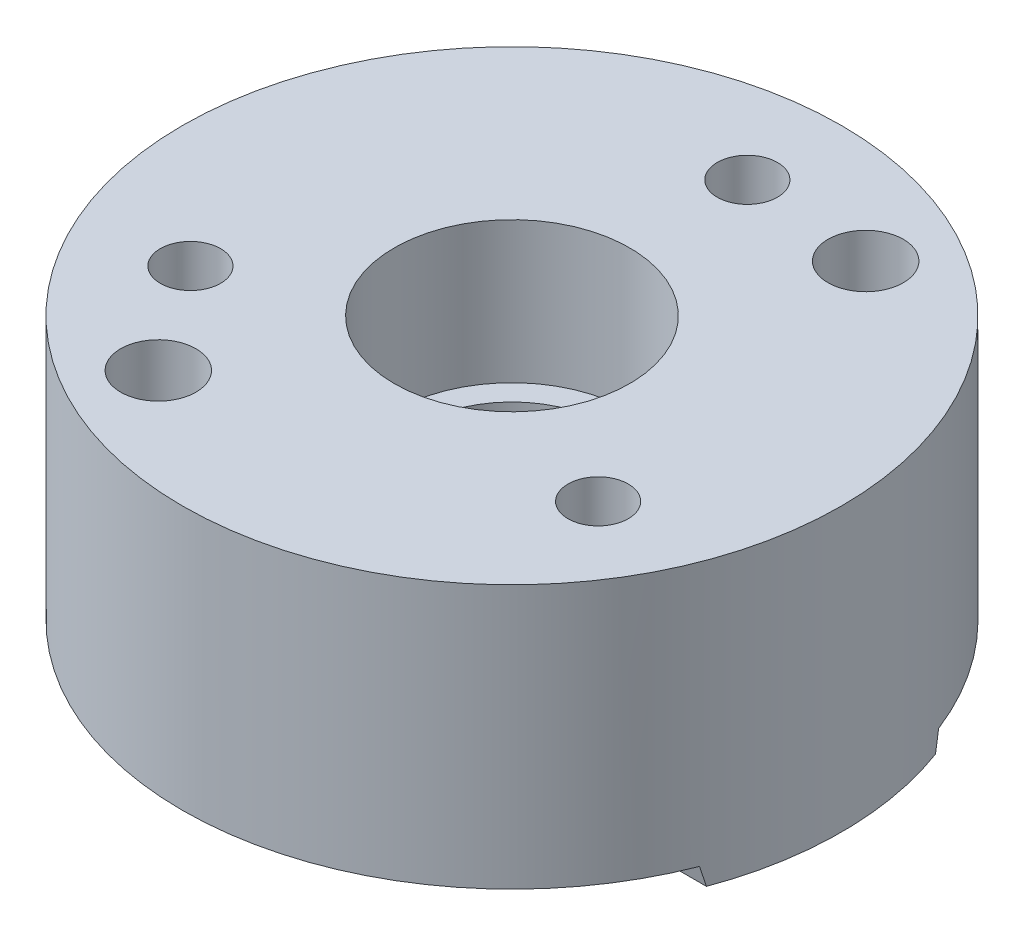
SolidWorks part; units mm, degrees
material "K110"
ref_plane "Front Plane" through (0, 0, 0) normal (0, 0, 1) x (1, 0, 0)
ref_plane "Top Plane" through (0, 0, 0) normal (0, 1, 0) x (1, 0, 0)
ref_plane "Right Plane" through (0, 0, 0) normal (1, 0, 0) x (0, 0, -1)
sketch "Sketch1" plane through (0, 0, 0) normal (0, 1, 0) x (1, 0, 0)
  circle A0 centre (0, 0) radius 35
  circle A1 centre (0, 0) radius 10
  dimension "D1" = 20
  dimension "D2" = 70
extrude "Boss-Extrude1" add sketch "Sketch1" against normal blind 30
sketch "Sketch4" plane through (0, 0, 0) normal (0, 1, 0) x (1, 0, 0)
  circle A0 centre (0, 0) radius 12.5
  dimension "D1" = 25
extrude "Cut-Extrude2" cut sketch "Sketch4" against normal blind 15
hole_wizard "CBORE for M6 Hex Socket Head Cap Screw1" positions "Sketch15" profile "Sketch8" counterbore size "M6" standard "ISO" end condition through all
sketch "Sketch15" plane through (0, -30, 0) normal (0, -1, 0) x (-1, 0, 0)
  line L0 (0, 25) -> (0, 0) construction
  line L1 (0, 0) -> (-21.6506, -12.5) construction
  line L3 (0, 0) -> (21.6506, -12.5) construction
  circle A0 centre (0, 0) radius 25 construction
  point P0 (0, 25)
  point P2 (21.6506, -12.5)
  point P4 (-21.6506, -12.5)
  dimension "D1" = 50
  dimension "D2" = 120
  dimension "D3" = 120
sketch "Sketch8" plane through (0, -30, -25) normal (1, 0, 0) x (0, 0, -1)
  line L0 (0, 0) -> (0, 30)
  line L1 (0, 30) -> (3.2, 30)
  line L3 (3.2, 30) -> (3.2, 8.4)
  line L4 (3.2, 8.4) -> (5.5, 8.4)
  line L5 (5.5, 8.4) -> (5.5, 0)
  line L7 (5.5, 0) -> (0, 0)
  line L11 (0, -6.35) -> (0, 107.95) construction
  dimension "Thru Hole Dia." = 6.4
  dimension "Thru Hole Depth" = 30
  dimension "C'Bore Dia." = 11
  dimension "C'Bore Depth" = 8.4
hole_wizard "Ø8.0mm Dowel Hole1" positions "Sketch17" profile "Sketch12" hole size "Ø8.0" standard "ISO" end condition through all
sketch "Sketch17" plane through (0, -30, 0) normal (0, -1, 0) x (-1, 0, 0)
  line L0 (-13.75, 23.8157) -> (13.75, -23.8157) construction
  line L1 (0, 35) -> (0, -35) construction
  circle A0 centre (0, 0) radius 27.5 construction
  circle A1 centre (0, 0) radius 35 construction
  point P0 (13.75, -23.8157)
  point P2 (-13.75, 23.8157)
  point P26 (0, 0)
  dimension "D1" = 55
  dimension "D2" = 30
sketch "Sketch12" plane through (-13.75, -30, 23.8157) normal (1, 0, 0) x (0, 0, -1)
  line L0 (0, 0) -> (0, 30)
  line L1 (0, 30) -> (4, 30)
  line L2 (4, 30) -> (4, 0)
  line L5 (4, 0) -> (0, 0)
  line L11 (0, -6.35) -> (0, 107.95) construction
  dimension "Thru Hole Dia." = 8
  dimension "Thru Hole Depth" = 30
sketch "Sketch14" plane through (0, -30, 0) normal (0, -1, 0) x (1, 0, 0)
  line L0 (-58.6405, -12.7) -> (-12.0399, -12.7) construction
  line L1 (-35, 12.7) -> (35, 12.7)
  line L2 (-35, 12.7) -> (-35, -12.7)
  line L3 (-35, -12.7) -> (35, -12.7)
  line L4 (35, 12.7) -> (35, -12.7)
  line L5 (-35, 12.7) -> (35, -12.7) construction
  line L6 (-35, -12.7) -> (35, 12.7) construction
  circle A0 centre (0, 0) radius 35 construction
  point P0 (0, 0)
extrude "Cut-Extrude3" cut sketch "Sketch14" against normal blind 2 flip side to cut
sketch "Sketch16" plane through (0, -30, 0) normal (0, -1, 0) x (1, 0, 0)
  circle A0 centre (22.5, 0) radius 4.25
  dimension "D1" = 8.5
sketch "Sketch18" plane through (0, -30, 0) normal (0, -1, 0) x (1, 0, 0)
  circle A1 centre (-25.9, 0) radius 4.25
  dimension "D1" = 8.5
extrude "Cut-Extrude5" cut sketch "Sketch18" against normal blind 6
sketch "Sketch19" plane through (0, 0, 0) normal (1, 0, 0) x (0, 0, -1)
  line L2 (-12.7, -28) -> (-12.1641, -30)
  line L3 (-12.7, -30) -> (12.7, -30) construction
  line L4 (-12.1641, -30) -> (-12.7, -30)
  line L5 (-12.7, -30) -> (-12.7, -28)
  line L6 (12.7, -28) -> (12.1641, -30)
  line L7 (12.1641, -30) -> (12.7, -30)
  line L8 (12.7, -30) -> (12.7, -28)
  dimension "D1" = 15
  dimension "D2" = 15
extrude "Cut-Extrude6" cut sketch "Sketch19" against normal through all both and the other way through all
sketch "Sketch20" plane through (0, -30, 0) normal (0, -1, 0) x (1, 0, 0)
  line L0 (-16.1609, 12.1641) -> (16.1609, 12.1641) construction
  line L1 (-12.5811, 12.1641) -> (12.5811, 12.1641)
  line L2 (-32.8182, -12.1641) -> (32.8182, -12.1641) construction
  line L3 (-12.5811, -12.1641) -> (12.5811, -12.1641)
  arc A0 (12.5811, 12.1641) -> (-12.5811, 12.1641) centre (0, 0) ccw
  arc A1 (-12.5811, -12.1641) -> (12.5811, -12.1641) centre (0, 0) ccw
  dimension "D1" = 35
extrude "Boss-Extrude2" add sketch "Sketch20" against normal up to surface (2 mm away) up to face at (13.75, -28, -27.8157)
draft "Draft1" type of draft neutral plane draft angle 3 faces to draft 1 face at (0, -28.9945, -14.9675) neutral plane through (0, -28, 0) neutral plane normal (0, -1, 0) parameters "D1"=3
